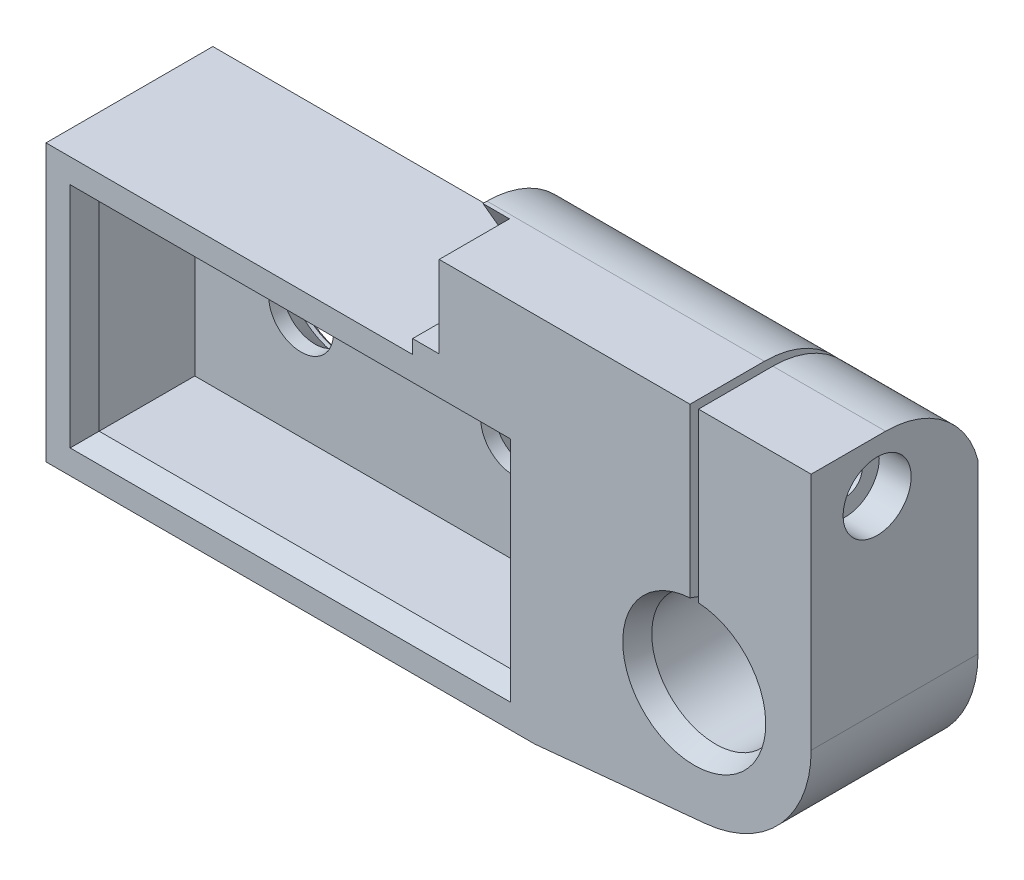
SolidWorks part; units mm, degrees
material "Custom Plastic"
ref_plane "Front Plane" through (0, 0, 0) normal (0, 0, 1) x (1, 0, 0)
ref_plane "Top Plane" through (0, 0, 0) normal (0, 1, 0) x (1, 0, 0)
ref_plane "Right Plane" through (0, 0, 0) normal (1, 0, 0) x (0, 0, -1)
sketch "Sketch1" plane through (0, 0, 0) normal (0, 0, 1) x (1, 0, 0)
  line L0 (-58, 10.5) -> (-18, -9.5) construction
  line L1 (-18, 10.5) -> (-58, 10.5) construction
  line L2 (-18, 10.5) -> (-18, -9.5) construction
  line L3 (-18, -9.5) -> (-58, -9.5) construction
  line L4 (-58, 10.5) -> (-58, -9.5) construction
  line L5 (-58, -9.5) -> (-18, 10.5) construction
  line L6 (-61, 13.5) -> (-61, -12.5)
  line L7 (-15, 13.5) -> (-61, 13.5) construction
  line L8 (-15, 13.5) -> (1.7126, 10.8659) construction
  line L10 (-48, 0.5) -> (-28, 0.5) construction
  line L11 (-61, -12.5) -> (-15, -12.5)
  line L12 (-15, -12.5) -> (-61, -12.5) construction
  line L13 (-15, 13.5) -> (-15, -12.5) construction
  line L14 (-15, -12.5) -> (1.0575, -10.949)
  line L15 (11, 0) -> (11, 22.5)
  line L16 (11, 22.5) -> (-26.5, 22.5)
  line L17 (-61, 13.5) -> (-26.5, 13.5)
  line L18 (-26.5, 13.5) -> (-26.5, 22.5)
  circle A0 centre (0, 0) radius 6 construction
  arc A1 (1.0575, -10.949) -> (11, 0) centre (0, 0) ccw
  circle A2 centre (-48, 0.5) radius 2.5
  circle A3 centre (-28, 0.5) radius 3.1
  point P11 (0, 0)
  point P12 (-38, 0.5)
  point P13 (9.6881, 0)
  dimension "D3" = 12
  dimension "D4" = 5
  dimension "D8" = 5
  dimension "D10" = 6.2
  dimension "D2" = 20
  dimension "D5" = 38
  dimension "D6" = 0.5
  dimension "D7" = 40
  dimension "D9" = 20
  dimension "D11" = 9
  dimension "D12" = 37.5
  dimension "D1" = 3
extrude "Boss-Extrude1" add sketch "Sketch1" along normal blind 16
sketch "Sketch2" plane through (0, 0, 16) normal (0, 0, 1) x (1, 0, 0)
  line L0 (-61, 13.5) -> (-61, -12.5) construction
  line L1 (-58, 10.5) -> (-18, 10.5)
  line L2 (-58, 10.5) -> (-58, -9.5)
  line L3 (-58, -9.5) -> (-18, -9.5)
  line L4 (-18, 10.5) -> (-18, -9.5)
  line L6 (-61, -12.5) -> (-15, -12.5) construction
  dimension "D1" = 3
  dimension "D2" = 3
  dimension "D3" = 20
  dimension "D4" = 40
extrude "Cut-Extrude1" cut sketch "Sketch2" against normal offset from surface (11 mm away) 5 up to face at (-45.5, 0.5, 0)
fillet "Fillet2" radius 9 1 edges at (-7.75, 22.5, 0)
sketch "Sketch3" plane through (0, 0, 16) normal (0, 0, 1) x (1, 0, 0)
  circle A0 centre (0, 0) radius 6
  dimension "D1" = 12
extrude "Cut-Extrude2" cut sketch "Sketch3" against normal offset from surface (11 mm away) 5 up to face at (-45.5, 0.5, 0)
sketch "Sketch6" plane through (0, 0, 16) normal (0, 0, 1) x (1, 0, 0)
  line L9 (-0.4, 24.3347) -> (0.4, 24.3347)
  line L10 (-0.4, 24.3347) -> (-0.4, 2.9732)
  line L15 (0.4, 24.3347) -> (0.4, 2.9732)
  line L16 (-0.4, 24.3347) -> (0.4, 2.9732) construction
  line L17 (-0.4, 2.9732) -> (0.4, 24.3347) construction
  arc A1 (-0.4, 2.9732) -> (0.4, 2.9732) centre (0, 0) ccw
  point P3 (0.1507, 0.3705)
  point P6 (0, 13.6539)
  point P7 (-14.5521, 6.3495)
  point P9 (-0.1507, -0.3705)
  point P10 (-15.3521, 5.8112)
  dimension "D4" = 3
  dimension "D3" = 0.8
extrude "Cut-Extrude5" cut sketch "Sketch6" against normal through all
sketch "Sketch7" plane through (0, 0, 0) normal (0, 0, -1) x (-1, 0, 0)
  line L0 (38, 10.5) -> (58, -9.5) construction
  line L1 (58, 10.5) -> (48, 0.5) construction
  line L3 (58, 10.5) -> (18, 10.5) construction
  circle A0 centre (48, 0.5) radius 3.05
  dimension "D1" = 6.1
extrude "Cut-Extrude6" cut sketch "Sketch7" against normal through all
sketch "Sketch8" plane through (0, 0, 16) normal (0, 0, 1) x (1, 0, 0)
  line L0 (-51.5, 9.5) -> (-44.5, 9.5) construction
  line L1 (-48, 9.5) -> (-48, 0.5) construction
  line L2 (-58, 10.5) -> (-18, 10.5) construction
  line L3 (-18, 10.5) -> (-58, 10.5) construction
  line L4 (-48, 12.2222) -> (-51.8111, 8.4111)
  line L5 (-51.8111, 8.4111) -> (-48, 4.6)
  line L6 (-48, 4.6) -> (-44.1889, 8.4111)
  line L7 (-44.1889, 8.4111) -> (-48, 12.2222)
  circle A0 centre (-51.5, 9.5) radius 0.55 construction
  circle A1 centre (-44.5, 9.5) radius 0.55 construction
  circle A2 centre (-48, 8.4111) radius 2.6948 construction
  dimension "D1" = 1.1
  dimension "D2" = 7
  dimension "D3" = 1
  dimension "D4" = 5.9
extrude "Boss-Extrude2" [suppressed] add sketch "Sketch8" against normal up to next
ref_axis "Axis1" through (-48, 0.5, 5) along (0, 0, -1)
pattern_circular "CirPattern1" [suppressed] count 2 over 360 about axis through (-48, 0.5, 5) along (0, 0, -1) of bodies 108
fillet "Fillet1" [suppressed] radius 0.8
chamfer "Chamfer2" distance 2 angle 20 4 edges at (-18, 0.5, 16) (-38, 10.5, 16) (-58, 0.5, 16) (-38, -9.5, 16) first distance on face at (-18, 0.5, 10.5) first distance on face at (-38, 10.5, 10.5) first distance on face at (-58, 0.5, 10.5) first distance on face at (-38, -9.5, 10.5)
sketch "Sketch10" plane through (0, 0, 0) normal (0, 0, -1) x (-1, 0, 0)
  circle A0 centre (28, 0.5) radius 6.1
  circle A1 centre (48, 0.5) radius 6.1
  dimension "D1" = 12.2
extrude "Cut-Extrude8" cut sketch "Sketch10" against normal blind 0.7
chamfer "Chamfer3" distance 3 angle 45 2 edges at (-51.05, 0.5, 0.7) (-31.1, 0.5, 0.7)
chamfer "Chamfer4" distance 0.3 angle 45 11 edges at (0, -3, 0) (-61, 0.5, 0) (-38, -12.5, 0) (-6.9712, -11.7245, 0) (8.1435, -7.3948, 0) (-34.1, 0.5, 0) (-54.1, 0.5, 0) (0.4, 8.2366, 0) (-0.4, 8.2366, 0) (11, 6.75, 0) (-43.75, 13.5, 0) tangent propagation no
sketch "Sketch11" plane through (11, 0, 0) normal (1, 0, 0) x (0, 0, -1)
  line L1 (-16, 13.5) -> (-0.3, 13.5) construction
  circle A0 centre (-9.7903, 17.6) radius 1.6
  circle A1 centre (-9.7903, 17.6) radius 3.1 construction
  point P3 (-9.7903, 14.5)
  dimension "D1" = 3.2
  dimension "D2" = 6.2
  dimension "D3" = 1
extrude "Cut-Extrude9" cut sketch "Sketch11" against normal through all
sketch "Sketch12" plane through (11, 0, 0) normal (1, 0, 0) x (0, 0, -1)
  circle A0 centre (-9.7903, 17.6) radius 3.2
  dimension "D1" = 6.4
extrude "Cut-Extrude10" cut sketch "Sketch12" against normal blind 3
sketch "Sketch13" plane through (11, 0, 0) normal (1, 0, 0) x (0, 0, -1)
  line L0 (-9.3862, 22.5) -> (-16, 22.5)
  line L1 (-6.5571, 17.6) -> (-9.3862, 22.5)
  line L2 (-8.2925, 20.4) -> (-11.4069, 20.4) construction
  line L3 (-11.4069, 20.4) -> (-13.0235, 17.6) construction
  line L4 (-13.0235, 17.6) -> (-11.3764, 14.7471) construction
  line L5 (-16, 14.8) -> (-8.1737, 14.8)
  line L6 (-8.1737, 14.8) -> (-6.5571, 17.6)
  line L8 (-16, 22.5) -> (-16, 14.8)
  line L10 (-16, 0) -> (-16, 22.5) construction
  line L11 (-16, 22.5) -> (-9, 22.5) construction
  circle A0 centre (-9.7903, 17.6) radius 2.8 construction
  dimension "D1" = 5.6
extrude "Cut-Extrude11" cut sketch "Sketch13" against normal through all from offset 35 offset against normal yes
chamfer "Chamfer5" distance 2 angle 20 1 edges at (0, -6, 16) first distance on face at (0, -0.0067, 10.5)
sketch "Sketch14" plane through (11, 0, 0) normal (1, 0, 0) x (0, 0, -1)
  line L0 (-9.7903, 17.6) -> (-10.9217, 18.7314)
  line L1 (-10.9217, 18.7314) -> (-11.7103, 17.9427)
  line L2 (-11.7103, 17.9427) -> (-11.7103, 17.2573)
  line L3 (-11.7103, 17.2573) -> (-10.9217, 16.4686)
  line L4 (-10.9217, 16.4686) -> (-9.7903, 17.6)
  circle A0 centre (-9.7903, 17.6) radius 1.6 construction
  point P8 (-11.3903, 17.6)
  dimension "D1" = 0.32
extrude "Cut-Extrude12" cut sketch "Sketch14" against normal through all
